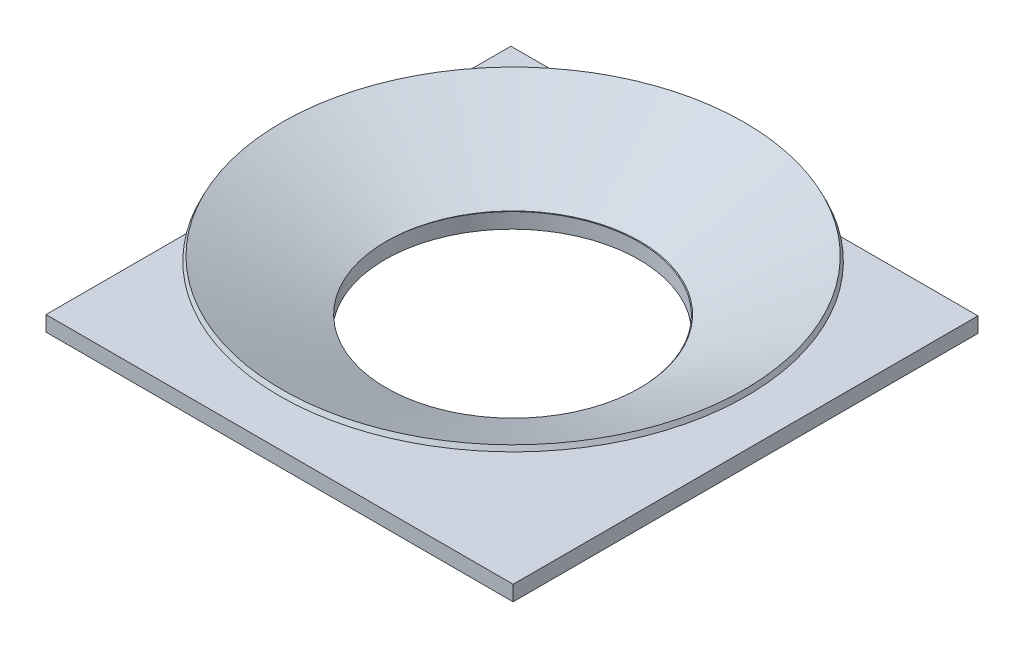
SolidWorks part; units mm, degrees
ref_plane "Front Plane" through (0, 0, 0) normal (0, 0, 1) x (1, 0, 0)
ref_plane "Top Plane" through (0, 0, 0) normal (0, 1, 0) x (1, 0, 0)
ref_plane "Right Plane" through (0, 0, 0) normal (1, 0, 0) x (0, 0, -1)
sketch "Sketch1" plane through (0, 0, 0) normal (0, 0, 1) x (1, 0, 0)
  line L0 (-27.2865, 0) -> (-46, 9.1007)
  line L1 (-46, 9.1007) -> (-45.5627, 10)
  line L2 (-45.5627, 10) -> (-25, 0)
  line L3 (-27.2865, 0) -> (-25, 0)
  line L4 (0, 0) -> (0, 38.049) construction
  line L5 (0, 0) -> (-37.9362, 0) construction
  dimension "D1" = 25
  dimension "D2" = 46
  dimension "D3" = 1
  dimension "D4" = 10
revolve "Revolve1" add sketch "Sketch1" angle 360 about L4
sketch "Sketch2" plane through (0, 0, 0) normal (0, 1, 0) x (1, 0, 0)
  line L0 (-46, -46) -> (46, -46)
  line L1 (-46, -46) -> (-46, 45.5627)
  line L2 (46, -46) -> (46, 45.5627)
  line L3 (-46, 45.5627) -> (46, 45.5627)
  line L4 (-46, -46) -> (46, 45.5627) construction
  line L5 (46, -46) -> (-46, 45.5627) construction
  circle A0 centre (0, -0.2187) radius 25
  circle A1 centre (0, 0) radius 46 construction
  circle A2 centre (0, 0) radius 45.5627 construction
  point P1 (0, -0.2187)
  point P3 (169.0258, -154.8303)
  dimension "D1" = 50
extrude "Boss-Extrude1" add sketch "Sketch2" against normal blind 3 separate body
